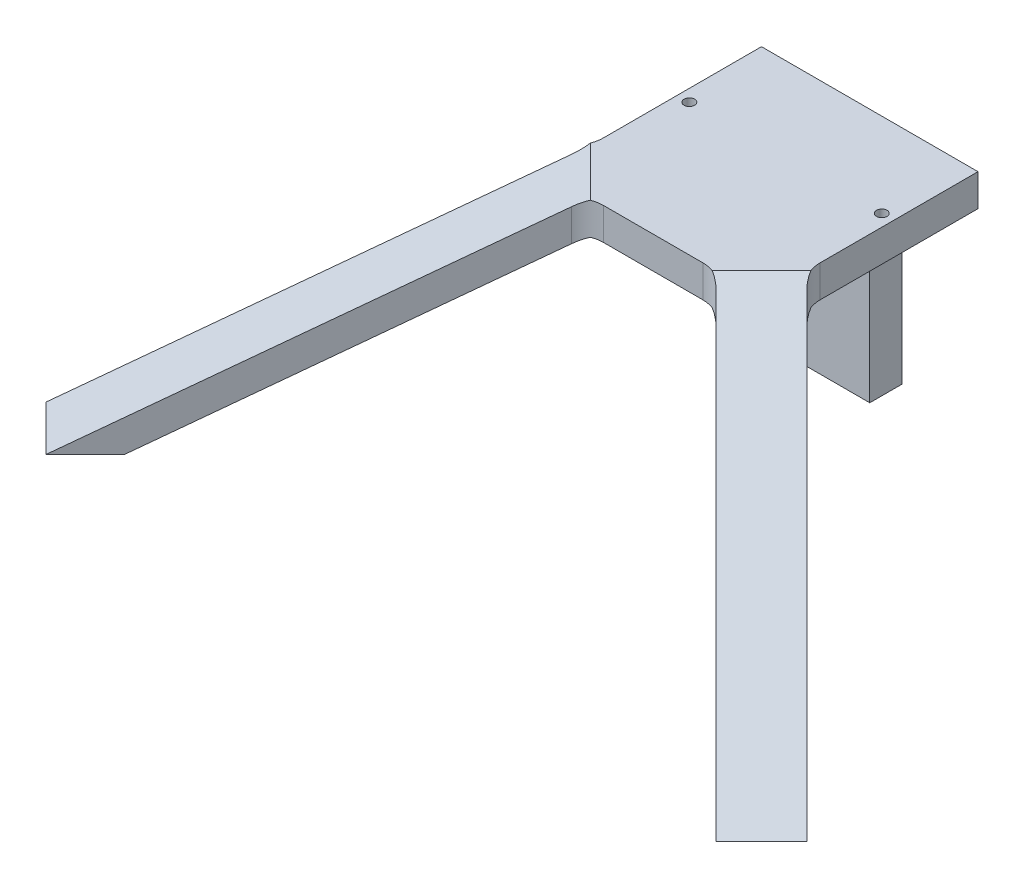
SolidWorks part; units mm, degrees
ref_plane "Front Plane" through (0, 0, 0) normal (0, 0, 1) x (1, 0, 0)
ref_plane "Top Plane" through (0, 0, 0) normal (0, 1, 0) x (1, 0, 0)
ref_plane "Right Plane" through (0, 0, 0) normal (1, 0, 0) x (0, 0, -1)
sketch "Sketch1" plane through (0, 0, 0) normal (0, 1, 0) x (1, 0, 0)
sketch "Sketch2" plane through (0, 0, 0) normal (0, 1, 0) x (1, 0, 0)
  line L0 (-33.75, -33.75) -> (33.75, -33.75)
  line L1 (-33.75, -33.75) -> (-33.75, 33.75)
  line L2 (33.75, -33.75) -> (33.75, 33.75)
  line L3 (-33.75, 33.75) -> (33.75, 33.75)
  line L4 (0, -1000) -> (0, 49000) construction
  circle A0 centre (0, 0) radius 20
  circle A1 centre (-30, 7.5) radius 1.65
  circle A2 centre (30, 7.5) radius 1.65
  point P0 (0, 33.75)
  point P6 (-33.75, 0)
  point P14 (0, 0)
  dimension "D4" = 40
  dimension "D1" = 3.3
  dimension "D2" = 67.5
  dimension "D3" = 67.5
  dimension "D5" = 3.75
  dimension "D6" = 26.25
extrude "Boss-Extrude3" add sketch "Sketch2" along normal blind 10 contours A0 L4 | L4 A0 | L0 L4 A0 L3 L1 A1 | L4 L0 L2 L3 A0 A2 region at (-20.0173, 0, 0.0391) region at (20.0173, 0, 0.0391) region at (-8.4883, 0, 0) region at (8.4883, 0, 0)
sketch "Sketch3" plane through (-30, 0, 30) normal (0, -1, 0) x (1, 0, 0)
  line L0 (-3.75, 3.75) -> (63.75, -63.75) construction
  line L1 (63.75, 3.75) -> (-3.75, -63.75) construction
ref_plane "Plane2" through (0, 0, 0) normal (0.7071, 0, 0.7071) x (0.7071, 0, -0.7071)
ref_plane "Plane3" through (0, 0, 0) normal (0.7071, 0, -0.7071) x (-0.7071, 0, -0.7071)
sketch "Sketch5" plane through (0, 0, 0) normal (0.7071, 0, 0.7071) x (0.7071, 0, -0.7071)
  line L0 (-37.7297, 10) -> (-157.7297, -59.282)
  line L1 (-47.7297, 10) -> (-47.7297, 0) construction
  line L2 (-37.7297, 0) -> (-140.4092, -59.282)
  line L3 (-157.7297, -59.282) -> (-140.4092, -59.282)
  line L5 (-37.7297, 10) -> (-37.7297, 0)
  line L6 (-47.7297, 10) -> (0, 10) construction
  line L7 (-47.7297, 0) -> (47.7297, 0) construction
  point P8 (0, 0)
  point P9 (0, 0)
  dimension "D1" = 60
  dimension "D2" = 10
  dimension "D3" = 120
extrude "Boss-Extrude6" add sketch "Sketch5" along normal blind 10 and the other way blind 10 contours L2 L3 L0 L5
sketch "Sketch8" plane through (-9.7316, 23.8374, 9.7316) normal (-0.3536, 0.866, 0.3536) x (0.9259, 0.2704, 0.2637)
  line L4 (-98.3001, -134.4339) -> (-81.476, -145.2482)
  line L5 (-81.476, -145.2482) -> (-6.5522, -28.6874)
  line L6 (-6.5522, -28.6874) -> (-21.2079, -32.9937)
  line L7 (-23.3763, -17.8731) -> (-98.3001, -134.4339)
  line L8 (-98.3001, -134.4339) -> (-81.476, -145.2482)
  line L9 (-81.476, -145.2482) -> (-6.5522, -28.6874)
  line L11 (-23.3763, -17.8731) -> (-98.3001, -134.4339)
  line L13 (-6.5522, -28.6874) -> (-21.2079, -32.9937)
  line L14 (-21.2079, -32.9937) -> (-23.3763, -17.8731)
  line L15 (-21.2079, -32.9937) -> (-23.3763, -17.8731)
  dimension "D1" = 0
mirror "Mirror3" about plane through (0, 0, 0) normal (1, 0, 0) of "Boss-Extrude6"
sketch "Sketch11" plane through (9.7316, 23.8374, 9.7316) normal (0.3536, 0.866, 0.3536) x (0.9259, -0.2704, -0.2637)
  line L0 (6.5522, -28.6874) -> (23.3763, -17.8731)
  line L1 (23.3763, -17.8731) -> (23.3763, -36.3671)
  line L2 (22.3506, -34.7713) -> (-22.3506, 34.7713) construction
  line L3 (28.389, -44.1655) -> (-28.389, 44.1655) construction
  line L4 (23.3763, -36.3671) -> (6.5522, -28.6874)
extrude "Cut-Extrude2" cut sketch "Sketch11" along normal blind 10 contours L4 L0 L1
sketch "Sketch12" plane through (-9.7316, 23.8374, 9.7316) normal (-0.3536, 0.866, 0.3536) x (0.9259, 0.2704, 0.2637)
  line L2 (-6.5522, -28.6874) -> (-23.3763, -17.8731)
  line L3 (-23.3763, -17.8731) -> (-21.2079, -32.9937)
  line L12 (-21.2079, -32.9937) -> (-6.5522, -28.6874)
sketch "Sketch13" plane through (0, 0, 0) normal (0, -1, 0) x (1, 0, 0)
  line L0 (-33.75, -33.75) -> (33.75, -33.75) construction
  line L1 (-10, -33.75) -> (10, -33.75)
  line L2 (-10, -33.75) -> (-10, -23.75)
  line L3 (-10, -23.75) -> (10, -23.75)
  line L4 (10, -33.75) -> (10, -23.75)
  point P6 (0, -23.75)
  dimension "D1" = 20
  dimension "D2" = 10
extrude "Cut-Extrude3" cut sketch "Sketch12" along normal blind 10
extrude "Boss-Extrude8" add sketch "Sketch13" along normal up to surface (59.282 mm away) up to face at (105.408, -59.282, 105.408)
fillet "Fillet1" radius 10 2 edges at (19.6079, 5, 33.75) (33.75, 5, 19.6079)
fillet "Fillet2" radius 10 2 edges at (-33.75, 5, 19.6079) (-19.6079, 5, 33.75)
